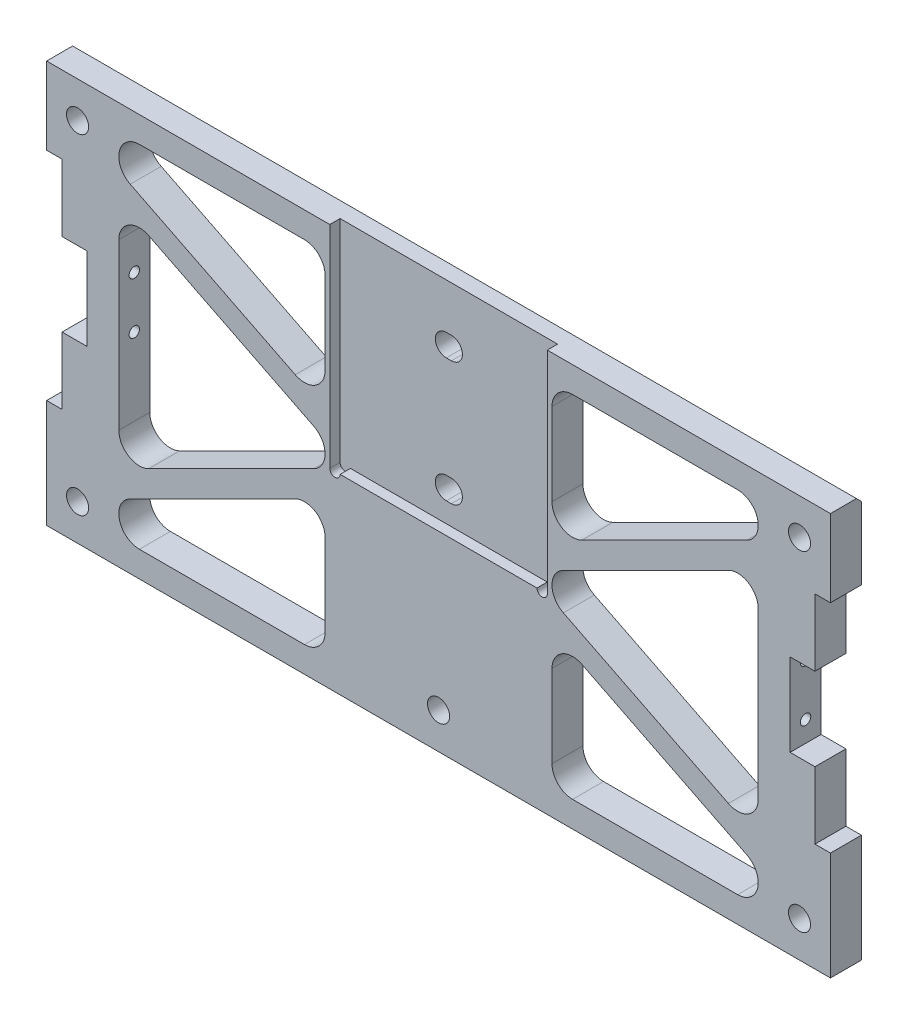
SolidWorks part; units mm, degrees
material "6061-T6 (SS)"
ref_plane "Front Plane" through (0, 0, 0) normal (0, 0, 1) x (1, 0, 0)
ref_plane "Top Plane" through (0, 0, 0) normal (0, 1, 0) x (1, 0, 0)
ref_plane "Right Plane" through (0, 0, 0) normal (1, 0, 0) x (0, 0, -1)
sketch "Sketch1" plane through (0, 0, 0) normal (0, 0, 1) x (1, 0, 0)
  line L0 (0, -2.6194) -> (0, 2.6194) construction
  line L1 (-60.325, 30.9562) -> (60.325, 30.9562)
  line L2 (-60.325, 30.9562) -> (-60.325, -30.9562)
  line L3 (-60.325, -30.9562) -> (60.325, -30.9562)
  line L4 (60.325, 30.9562) -> (60.325, -30.9562)
  line L5 (2.6194, 0) -> (-2.6194, 0) construction
  point P4 (0, 30.9562)
  point P7 (-60.325, 0)
  dimension "D1" = 120.65
  dimension "D2" = 61.9125
extrude "Boss-Extrude1" add sketch "Sketch1" along normal blind 4.7625
sketch "Sketch2" plane through (0, 0, 4.7625) normal (0, 0, 1) x (1, 0, 0)
  line L0 (-60.325, 30.9562) -> (-60.325, -30.9562) construction
  line L1 (-60.325, 8.7439) -> (-55.5625, 8.7439)
  line L2 (-60.325, 8.7439) -> (-60.325, -3.9815)
  line L3 (-60.325, -3.9815) -> (-55.5625, -3.9815)
  line L4 (-55.5625, 8.7439) -> (-55.5625, -3.9815)
  line L5 (-60.325, 2.3812) -> (-55.5625, 2.3812) construction
  line L7 (60.325, 30.9562) -> (-60.325, 30.9562) construction
  dimension "D1" = 12.7254
  dimension "D2" = 4.7625
  dimension "D3" = 28.575
extrude "Boss-Extrude2" add sketch "Sketch2" along normal blind 22.225
sketch "Sketch3" plane through (-60.325, 0, 0) normal (-1, 0, 0) x (0, 0, 1)
  line L0 (0, -34.0519) -> (0, 34.0519) construction
  line L1 (26.9875, -3.9815) -> (4.7625, -3.9815) construction
  circle A0 centre (19.05, 2.3685) radius 2.25
  dimension "D3" = 4.5
  dimension "D1" = 19.05
  dimension "D2" = 6.35
extrude "Cut-Extrude1" cut sketch "Sketch3" against normal up to next
fillet "Fillet1" radius 6.35 2 edges at (-57.9437, -3.9815, 26.9875) (-57.9437, 8.7439, 26.9875)
sketch "Sketch4" plane through (0, 0, 4.7625) normal (0, 0, 1) x (1, 0, 0)
  line L0 (-47.625, 23.0187) -> (-14.2875, 23.0187)
  line L1 (-47.625, -23.0187) -> (-14.2875, -23.0187)
  line L2 (-50.8, -19.8437) -> (-50.8, -6.35)
  line L3 (-11.1125, -19.8437) -> (-11.1125, -6.35)
  line L4 (-61.9089, 0) -> (61.2866, 0) construction
  line L5 (60.325, 30.9562) -> (-60.325, 30.9562) construction
  line L6 (-60.325, -30.9562) -> (60.325, -30.9562) construction
  line L7 (-60.325, -3.9815) -> (-60.325, -30.9562) construction
  line L8 (0, -2.6194) -> (0, 2.6194) construction
  line L9 (0, 46.547) -> (0, -45.6231) construction
  line L10 (50.8, 6.35) -> (50.8, 19.8437)
  line L11 (11.1125, 6.35) -> (11.1125, 19.8437)
  line L12 (14.2875, -3.175) -> (47.625, -3.175)
  line L13 (14.2875, 3.175) -> (47.625, 3.175)
  line L14 (-14.2875, 3.175) -> (-47.625, 3.175)
  line L15 (-14.2875, -3.175) -> (-47.625, -3.175)
  line L16 (-11.1125, 6.35) -> (-11.1125, 19.8437)
  line L17 (-50.8, 6.35) -> (-50.8, 19.8437)
  line L18 (11.1125, -19.8437) -> (11.1125, -6.35)
  line L19 (50.8, -19.8437) -> (50.8, -6.35)
  line L20 (47.625, -23.0187) -> (14.2875, -23.0187)
  line L21 (47.625, 23.0187) -> (14.2875, 23.0187)
  arc A0 (47.625, 3.175) -> (50.8, 6.35) centre (47.625, 6.35) ccw
  arc A1 (14.2875, 3.175) -> (11.1125, 6.35) centre (14.2875, 6.35) cw
  arc A2 (11.1125, -6.35) -> (14.2875, -3.175) centre (14.2875, -6.35) cw
  arc A3 (50.8, -6.35) -> (47.625, -3.175) centre (47.625, -6.35) ccw
  arc A4 (-11.1125, -19.8437) -> (-14.2875, -23.0187) centre (-14.2875, -19.8437) cw
  arc A5 (-47.625, -23.0187) -> (-50.8, -19.8437) centre (-47.625, -19.8437) cw
  arc A6 (-50.8, 19.8437) -> (-47.625, 23.0187) centre (-47.625, 19.8437) cw
  arc A7 (-14.2875, 23.0187) -> (-11.1125, 19.8437) centre (-14.2875, 19.8437) cw
  arc A8 (-50.8, -6.35) -> (-47.625, -3.175) centre (-47.625, -6.35) cw
  arc A9 (-11.1125, -6.35) -> (-14.2875, -3.175) centre (-14.2875, -6.35) ccw
  arc A10 (-14.2875, 3.175) -> (-11.1125, 6.35) centre (-14.2875, 6.35) ccw
  arc A11 (-47.625, 3.175) -> (-50.8, 6.35) centre (-47.625, 6.35) cw
  arc A12 (14.2875, 23.0187) -> (11.1125, 19.8437) centre (14.2875, 19.8437) ccw
  arc A13 (50.8, 19.8437) -> (47.625, 23.0187) centre (47.625, 19.8437) ccw
  arc A14 (47.625, -23.0187) -> (50.8, -19.8437) centre (47.625, -19.8437) ccw
  arc A15 (11.1125, -19.8437) -> (14.2875, -23.0187) centre (14.2875, -19.8437) ccw
  point P35 (-11.1125, -23.0187)
  point P38 (-50.8, -23.0187)
  point P41 (-50.8, 23.0187)
  point P44 (-11.1125, 23.0187)
  point P55 (-11.1125, 3.175)
  point P66 (11.1125, 3.175)
  point P67 (11.1125, 23.0187)
  point P68 (50.8, 23.0187)
  point P69 (50.8, -23.0187)
  point P70 (11.1125, -23.0187)
  dimension "D5" = 3.175
  dimension "D8" = 3.175
  dimension "D1" = 7.9375
  dimension "D2" = 7.9375
  dimension "D3" = 9.525
  dimension "D4" = 11.1125
  dimension "D6" = 3.175
  dimension "D7" = 6.35
extrude "Cut-Extrude2" [suppressed] cut sketch "Sketch4" against normal up to next
mirror "Mirror2" about plane through (0, 0, 0) normal (1, 0, 0) of "Fillet1", "Boss-Extrude2", "Cut-Extrude1"
hole_wizard "M3 Clearance Slot1" positions "Sketch5" profile "Sketch6" size "M3" standard "ANSI Metric" slot yes end condition up to next
sketch "Sketch5" plane through (0, 0, 0) normal (0, 0, -1) x (-1, 0, 0)
  line L2 (-60.325, 30.9562) -> (60.325, 30.9562) construction
  line L4 (2.0861, 22.2567) -> (-2.0861, 22.2567) construction
  line L5 (0, 2.6194) -> (0, -2.6194) construction
  point P0 (0, 22.2567)
  point P2 (0, 3.2067)
  dimension "D1" = 19.05
  dimension "D2" = 8.6995
  dimension "D4" = 4.1722
sketch "Sketch6" plane through (0, 22.2567, 0) normal (1, 0, 0) x (0, 1, 0)
  line L0 (0, 0) -> (0, 4.7625)
  line L1 (0, 4.7625) -> (1.7, 4.7625)
  line L2 (1.7, 4.7625) -> (1.7, 0)
  line L5 (1.7, 0) -> (0, 0)
  line L11 (0, -6.35) -> (0, 107.95) construction
  dimension "Thru Hole Dia." = 3.4
  dimension "Thru Hole Depth" = 4.7625
sketch "Sketch7" plane through (0, 0, 4.7625) normal (0, 0, 1) x (1, 0, 0)
  line L1 (-60.325, 8.7439) -> (-57.9437, 8.7439)
  line L2 (-60.325, 8.7439) -> (-60.325, 19.0627)
  line L3 (-60.325, 19.0627) -> (-57.9437, 19.0627)
  line L4 (-57.9437, 8.7439) -> (-57.9437, 19.0627)
  line L5 (-60.325, -3.9815) -> (-57.9437, -3.9815)
  line L6 (-60.325, -3.9815) -> (-60.325, -14.3002)
  line L7 (-60.325, -14.3002) -> (-57.9437, -14.3002)
  line L8 (-57.9437, -3.9815) -> (-57.9437, -14.3002)
  dimension "D1" = 10.3187
  dimension "D2" = 2.3813
extrude "Cut-Extrude3" cut sketch "Sketch7" against normal through all
sketch "Sketch8" plane through (-60.325, 0, 0) normal (-1, 0, 0) x (0, 0, 1)
  line L4 (0, 8.7439) -> (0, -3.9815)
  line L5 (0, -3.9815) -> (20.6375, -3.9815)
  line L6 (26.9875, 2.3685) -> (26.9875, 2.3939)
  line L7 (20.6375, 8.7439) -> (0, 8.7439)
  line L8 (0, 8.7439) -> (0, -3.9815)
  line L9 (0, -3.9815) -> (20.6375, -3.9815)
  line L10 (26.9875, 2.3685) -> (26.9875, 2.3939)
  line L11 (20.6375, 8.7439) -> (0, 8.7439)
  arc A2 (20.6375, -3.9815) -> (26.9875, 2.3685) centre (20.6375, 2.3685) ccw
  arc A3 (26.9875, 2.3939) -> (20.6375, 8.7439) centre (20.6375, 2.3939) ccw
  arc A4 (20.6375, -3.9815) -> (26.9875, 2.3685) centre (20.6375, 2.3685) ccw
  arc A5 (26.9875, 2.3939) -> (20.6375, 8.7439) centre (20.6375, 2.3939) ccw
  dimension "D1" = 0
extrude "Cut-Extrude4" cut sketch "Sketch8" against normal blind 6.2071
sketch "Sketch11" plane through (0, 0, 4.7625) normal (0, 0, 1) x (1, 0, 0)
  line L0 (-19.2176, 2.8398) -> (-44.6176, 15.5398)
  line L1 (-49.2125, 12.7) -> (-49.2125, -12.7)
  line L2 (-76.1551, 0) -> (76.2512, 0) construction
  line L3 (-19.2176, -2.8398) -> (-44.6176, -15.5398)
  line L4 (0, -2.6194) -> (0, 2.6194) construction
  arc A0 (-19.2176, -2.8398) -> (-19.2176, 2.8398) centre (-20.6375, 0) ccw
  arc A1 (-44.6176, -15.5398) -> (-49.2125, -12.7) centre (-46.0375, -12.7) cw
  arc A2 (-49.2125, 12.7) -> (-44.6176, 15.5398) centre (-46.0375, 12.7) cw
  point P9 (-49.2125, 0)
  point P11 (-49.2125, -17.8373)
  point P14 (-49.2125, 17.8373)
  dimension "D1" = 6.35
  dimension "D2" = 6.35
  dimension "D3" = 25.4
  dimension "D4" = 20.6375
  dimension "D5" = 25.4
extrude "Cut-Extrude5" cut sketch "Sketch11" against normal through all
sketch "Sketch12" plane through (0, 0, 4.7625) normal (0, 0, 1) x (1, 0, 0)
  line L0 (-47.4574, 20.9727) -> (-22.0574, 8.2727)
  line L1 (-17.4625, 11.1125) -> (-17.4625, 23.8125)
  line L2 (-20.6375, 26.9875) -> (-46.0375, 26.9875)
  line L3 (-19.2176, 2.8398) -> (-44.6176, 15.5398) construction
  line L4 (60.325, 30.9562) -> (-60.325, 30.9562) construction
  line L5 (-72.0059, 0) -> (76.9151, 0) construction
  line L6 (-20.6375, -26.9875) -> (-46.0375, -26.9875)
  line L7 (-17.4625, -11.1125) -> (-17.4625, -23.8125)
  line L8 (-47.4574, -20.9727) -> (-22.0574, -8.2727)
  arc A0 (-22.0574, 8.2727) -> (-17.4625, 11.1125) centre (-20.6375, 11.1125) ccw
  arc A1 (-17.4625, 23.8125) -> (-20.6375, 26.9875) centre (-20.6375, 23.8125) ccw
  arc A2 (-46.0375, 26.9875) -> (-47.4574, 20.9727) centre (-46.0375, 23.8125) ccw
  arc A4 (-19.2176, -2.8398) -> (-19.2176, 2.8398) centre (-20.6375, 0) ccw construction
  arc A5 (-46.0375, -26.9875) -> (-47.4574, -20.9727) centre (-46.0375, -23.8125) cw
  arc A6 (-17.4625, -23.8125) -> (-20.6375, -26.9875) centre (-20.6375, -23.8125) cw
  arc A7 (-22.0574, -8.2727) -> (-17.4625, -11.1125) centre (-20.6375, -11.1125) cw
  dimension "D1" = 3.9688
  dimension "D2" = 3.5893
extrude "Cut-Extrude6" cut sketch "Sketch12" against normal through all
hole_wizard "M2x0.4 Tapped Hole1" positions "Sketch9" profile "Sketch10" tap size "M2x0.4" standard "ANSI Metric" end condition up to next
sketch "Sketch9" plane through (-54.1179, 0, 0) normal (-1, 0, 0) x (0, 0, 1)
  point P0 (2.3813, 7.1438)
  point P4 (2.3813, -0.7937)
cosmetic thread "Hole Thread1" parameters "D2"=2
cosmetic thread "Hole Thread2" parameters "D2"=2
sketch "Sketch10" plane through (-54.1179, 7.1438, 2.3813) normal (0, 1, 0) x (0, 0, 1)
  line L0 (0, 0) -> (0, 4.9054)
  line L1 (0, 4.9054) -> (0.8, 4.9054)
  line L2 (0.8, 4.9054) -> (0.8, 0)
  line L5 (0.8, 0) -> (0, 0)
  line L11 (0, -6.35) -> (0, 107.95) construction
  dimension "Thru Tap Drill Dia." = 1.6
  dimension "Thru Tap Drill Depth" = 4.9054
mirror "Mirror4" about plane through (0, 0, 0) normal (1, 0, 0) of "Cut-Extrude5", "Cut-Extrude6"
mirror "Mirror3" about plane through (0, 0, 0) normal (1, 0, 0) of "M2x0.4 Tapped Hole1", "Cut-Extrude4", "Cut-Extrude3"
sketch "Sketch13" plane through (0, 0, 4.7625) normal (0, 0, 1) x (1, 0, 0)
  line L0 (-16.7386, 30.9562) -> (-16.7386, -1.5558)
  line L1 (60.325, 30.9562) -> (-60.325, 30.9562) construction
  line L2 (-15.1511, -1.5558) -> (15.1511, -1.5558)
  line L3 (16.7386, -1.5558) -> (16.7386, 30.9562)
  line L4 (16.7386, 30.9562) -> (-16.7386, 30.9562)
  line L5 (0, -2.6194) -> (0, 2.6194) construction
  arc A0 (-16.7386, -1.5558) -> (-15.1511, -1.5558) centre (-15.9449, -1.5558) ccw
  arc A1 (16.7386, -1.5558) -> (15.1511, -1.5558) centre (15.9449, -1.5558) cw
  dimension "D4" = 1.5875
  dimension "D1" = 33.4772
  dimension "D2" = 16.7386
  dimension "D3" = 32.512
extrude "Cut-Extrude7" cut sketch "Sketch13" against normal blind 1.5875
hole_wizard "M3 Clearance Hole2" positions "Sketch14" profile "Sketch15" hole size "M3" standard "ANSI Metric" end condition up to next
sketch "Sketch14" plane through (0, 0, 4.7625) normal (0, 0, 1) x (1, 0, 0)
  line L0 (0, -2.6194) -> (0, 2.6194) construction
  line L1 (2.6194, 0) -> (-2.6194, 0) construction
  line L2 (0, 36.8525) -> (0, -45.6827) construction
  point P0 (-55.5625, 25.4)
  point P2 (-55.5625, -25.4)
  point P4 (0, -25.4)
  point P18 (55.5625, 25.4)
  point P19 (55.5625, -25.4)
  dimension "D1" = 55.5625
  dimension "D2" = 25.4
  dimension "D3" = 25.4
sketch "Sketch15" plane through (-55.5625, 25.4, 4.7625) normal (1, 0, 0) x (0, -1, 0)
  line L0 (0, 0) -> (0, 4.7625)
  line L1 (0, 4.7625) -> (1.7, 4.7625)
  line L2 (1.7, 4.7625) -> (1.7, 0)
  line L5 (1.7, 0) -> (0, 0)
  line L11 (0, -6.35) -> (0, 107.95) construction
  dimension "Thru Hole Dia." = 3.4
  dimension "Thru Hole Depth" = 4.7625
chamfer "Chamfer1" distance 0.762 angle 45 1 edges at (0, 30.9562, 0)
